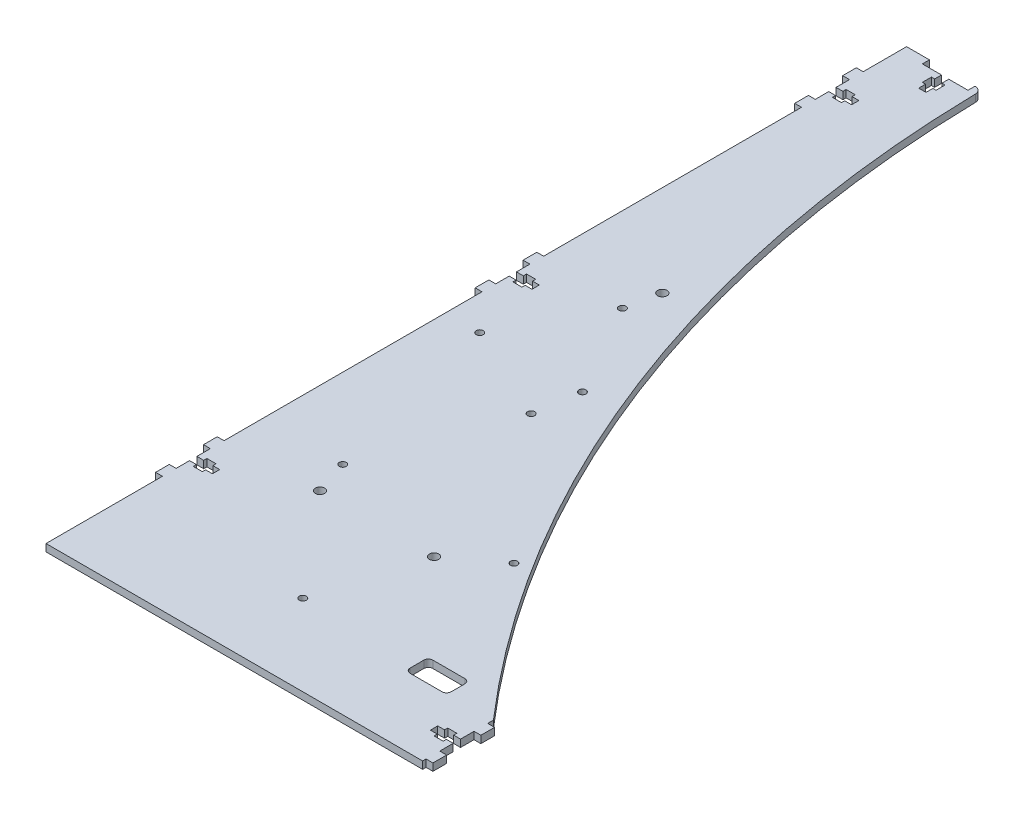
SolidWorks part; units mm, degrees
ref_plane "Alzado" through (0, 0, 0) normal (0, 0, 1) x (1, 0, 0)
ref_plane "Planta" through (0, 0, 0) normal (0, 1, 0) x (1, 0, 0)
ref_plane "Vista lateral" through (0, 0, 0) normal (1, 0, 0) x (0, 0, -1)
sketch "Croquis1" plane through (0, 0, 0) normal (0, 1, 0) x (1, 0, 0)
  line L0 (7, 66.1) -> (10, 66.1)
  line L1 (0, 0) -> (165, 0)
  line L2 (0, 0) -> (0, 51)
  line L3 (0, 377) -> (10, 377)
  line L4 (165, 0) -> (165, 1.5)
  line L5 (0, 51) -> (-3, 51)
  line L7 (0, 57) -> (-3, 57)
  line L8 (-3, 51) -> (-3, 57)
  line L9 (0, 72) -> (-3, 72)
  line L11 (0, 78) -> (-3, 78)
  line L12 (-3, 72) -> (-3, 78)
  line L13 (0, 66.1) -> (3, 66.1)
  line L15 (0, 62.9) -> (3, 62.9)
  line L16 (10, 66.1) -> (10, 62.9)
  line L17 (7, 67.5) -> (3, 67.5)
  line L18 (7, 67.5) -> (7, 66.1)
  line L19 (7, 61.5) -> (3, 61.5)
  line L20 (3, 67.5) -> (3, 66.1)
  line L21 (3, 62.9) -> (3, 61.5)
  line L22 (7, 62.9) -> (7, 61.5)
  line L23 (7, 62.9) -> (10, 62.9)
  line L24 (0, 66.1) -> (0, 72)
  line L25 (0, 78) -> (0, 191)
  line L26 (0, 57) -> (0, 62.9)
  line L27 (0, 218) -> (-3, 218)
  line L28 (-3, 212) -> (-3, 218)
  line L29 (0, 212) -> (-3, 212)
  line L30 (0, 206.1) -> (3, 206.1)
  line L31 (3, 207.5) -> (3, 206.1)
  line L32 (7, 207.5) -> (3, 207.5)
  line L33 (7, 207.5) -> (7, 206.1)
  line L34 (7, 206.1) -> (10, 206.1)
  line L35 (10, 206.1) -> (10, 202.9)
  line L36 (7, 202.9) -> (10, 202.9)
  line L37 (7, 202.9) -> (7, 201.5)
  line L38 (7, 201.5) -> (3, 201.5)
  line L39 (3, 202.9) -> (3, 201.5)
  line L40 (0, 202.9) -> (3, 202.9)
  line L41 (0, 197) -> (-3, 197)
  line L42 (-3, 191) -> (-3, 197)
  line L43 (0, 191) -> (-3, 191)
  line L44 (0, 358) -> (-3, 358)
  line L45 (-3, 352) -> (-3, 358)
  line L46 (0, 352) -> (-3, 352)
  line L47 (0, 346.1) -> (3, 346.1)
  line L48 (3, 347.5) -> (3, 346.1)
  line L49 (7, 347.5) -> (3, 347.5)
  line L50 (7, 347.5) -> (7, 346.1)
  line L51 (7, 346.1) -> (10, 346.1)
  line L52 (10, 346.1) -> (10, 342.9)
  line L53 (7, 342.9) -> (10, 342.9)
  line L54 (7, 342.9) -> (7, 341.5)
  line L55 (7, 341.5) -> (3, 341.5)
  line L56 (3, 342.9) -> (3, 341.5)
  line L57 (0, 342.9) -> (3, 342.9)
  line L58 (0, 337) -> (-3, 337)
  line L59 (-3, 331) -> (-3, 337)
  line L60 (0, 331) -> (-3, 331)
  line L61 (0, 358) -> (0, 377)
  line L62 (0, 346.1) -> (0, 352)
  line L63 (0, 337) -> (0, 342.9)
  line L64 (0, 218) -> (0, 331)
  line L65 (0, 206.1) -> (0, 212)
  line L66 (0, 197) -> (0, 202.9)
  line L67 (21.6, 373.9) -> (30, 373.9)
  line L69 (10, 377) -> (10, 373.9)
  line L70 (10, 373.9) -> (18.4, 373.9)
  line L71 (30, 377) -> (30, 373.9)
  line L73 (18.4, 373.9) -> (18.4, 370.9)
  line L74 (18.4, 363.9) -> (21.6, 363.9)
  line L75 (21.6, 373.9) -> (21.6, 370.9)
  line L76 (17, 370.9) -> (18.4, 370.9)
  line L77 (17, 370.9) -> (17, 366.9)
  line L78 (17, 366.9) -> (18.4, 366.9)
  line L79 (23, 370.9) -> (23, 366.9)
  line L80 (21.6, 370.9) -> (23, 370.9)
  line L81 (18.4, 366.9) -> (18.4, 363.9)
  line L82 (21.6, 366.9) -> (21.6, 363.9)
  line L83 (21.6, 366.9) -> (23, 366.9)
  line L84 (30, 377) -> (165, 377)
  line L85 (158, 13.4) -> (158, 12)
  line L86 (165, 1.5) -> (168, 1.5)
  line L88 (165, 7.5) -> (168, 7.5)
  line L89 (168, 1.5) -> (168, 7.5)
  line L90 (165, 22.5) -> (168, 22.5)
  line L92 (165, 28.5) -> (168, 28.5)
  line L93 (168, 22.5) -> (168, 28.5)
  line L94 (165, 16.6) -> (162, 16.6)
  line L96 (165, 13.4) -> (162, 13.4)
  line L97 (155, 16.6) -> (155, 13.4)
  line L98 (158, 18) -> (162, 18)
  line L99 (158, 18) -> (158, 16.6)
  line L100 (158, 12) -> (162, 12)
  line L101 (162, 18) -> (162, 16.6)
  line L102 (158, 16.6) -> (155, 16.6)
  line L103 (162, 13.4) -> (162, 12)
  line L104 (158, 13.4) -> (155, 13.4)
  line L105 (165, 16.6) -> (165, 22.5)
  line L106 (165, 7.5) -> (165, 13.4)
  line L107 (165, 28.5) -> (165, 377)
  dimension "D1" = 377
  dimension "D2" = 165
  dimension "D3" = 3
  dimension "D4" = 6
  dimension "D5" = 3
  dimension "D6" = 6
  dimension "D7" = 15
  dimension "D8" = 10
  dimension "D9" = 3.2
  dimension "D10" = 5.9
  dimension "D11" = 4
  dimension "D12" = 6
  dimension "D13" = 1.4
  dimension "D14" = 51
  dimension "D15" = 3
  dimension "D17" = 140
  dimension "D18" = 20
  dimension "D19" = 10
  dimension "D20" = 3.1
  dimension "D21" = 10
  dimension "D22" = 3.2
  dimension "D23" = 4
  dimension "D24" = 6
  dimension "D25" = 1.4
  dimension "D26" = 8.4
  dimension "D27" = 3
  dimension "D28" = 6
  dimension "D29" = 6
  dimension "D30" = 3
  dimension "D31" = 3
  dimension "D32" = 3.2
  dimension "D33" = 4
  dimension "D34" = 6
  dimension "D35" = 1.4
  dimension "D36" = 10
  dimension "D37" = 3
  dimension "D38" = 15
  dimension "D39" = 5.9
  dimension "D40" = 1.5
  dimension "D16" = 3
extrude "Saliente-Extruir1" add sketch "Croquis1" along normal blind 3.2
sketch "Croquis2" plane through (0, 0, 0) normal (0, -1, 0) x (1, 0, 0)
  line L0 (30, -377) -> (30, -373.9) construction
  line L1 (165, -377) -> (33, -377)
  line L2 (165, -377) -> (165, -31)
  line L3 (165, -31) -> (33, -31) construction
  line L4 (33, -377) -> (33, -31) construction
  line L5 (168, -28.5) -> (165, -28.5) construction
  arc A0 (33, -377) -> (165, -31) centre (571.7994, -384.3743) cw
  dimension "D1" = 3
  dimension "D2" = 2.5
extrude "Cortar-Extruir1" cut sketch "Croquis2" against normal up to surface (3.2 mm away) up to face at (40.46, 3.2, -192.526)
fillet "Redondeo1" radius 3 1 edges at (33, 1.6, -377)
sketch "Croquis3" plane through (0, 3.2, 0) normal (0, 1, 0) x (1, 0, 0)
  line L0 (0, 202.9) -> (0, 197) construction
  line L1 (0, 0) -> (165, 0) construction
  circle A0 centre (40, 80) radius 2.05
  circle A1 centre (90, 80) radius 2.05
  circle A2 centre (40, 230) radius 2.05
  dimension "D1" = 4.1
  dimension "D2" = 50
  dimension "D3" = 150
  dimension "D4" = 40
  dimension "D5" = 80
extrude "Cortar-Extruir2" cut sketch "Croquis3" against normal up to surface (3.2 mm away) up to face at (39.9955, 0, -192.6144)
sketch "Croquis4" plane through (0, 0, 0) normal (0, -1, 0) x (1, 0, 0)
  line L1 (0, 0) -> (165, 0) construction
  line L3 (165, -28.5) -> (165, -31) construction
  line L4 (143, -30.5) -> (129, -30.5)
  line L5 (145, -32.5) -> (145, -38.5)
  line L6 (143, -40.5) -> (129, -40.5)
  line L7 (127, -32.5) -> (127, -38.5)
  arc A14 (143, -30.5) -> (145, -32.5) centre (143, -32.5) cw
  arc A15 (127, -38.5) -> (129, -40.5) centre (129, -38.5) ccw
  arc A16 (127, -32.5) -> (129, -30.5) centre (129, -32.5) cw
  arc A17 (145, -38.5) -> (143, -40.5) centre (143, -38.5) cw
  point P38 (145, -30.5)
  point P41 (127, -40.5)
  point P46 (145, -40.5)
  dimension "D3" = 20
  dimension "D20" = 2
  dimension "D16" = 18
  dimension "D17" = 10
  dimension "D19" = 30.5
extrude "Cortar-Extruir3" cut sketch "Croquis4" against normal up to surface (3.2 mm away) up to face at (40, 3.2, -227.95)
sketch "Croquis5" plane through (0, 0, 0) normal (0, -1, 0) x (1, 0, 0)
  line L0 (0, 0) -> (165, 0) construction
  line L1 (0, -191) -> (0, -78) construction
  line L2 (127, -35.5) -> (77, -35.5) construction
  line L3 (127, -32.5) -> (127, -38.5) construction
  circle A0 centre (110, -95) radius 1.55
  circle A1 centre (35, -95) radius 1.55
  circle A2 centre (15, -175) radius 1.55
  circle A3 centre (60, -175) radius 1.55
  circle A4 centre (77, -35.5) radius 1.55
  circle A5 centre (37, -215.5) radius 1.55
  circle A6 centre (57, -155.5) radius 1.55
  dimension "D1" = 3.1
  dimension "D2" = 75
  dimension "D3" = 95
  dimension "D4" = 35
  dimension "D5" = 45
  dimension "D6" = 15
  dimension "D7" = 80
  dimension "D8" = 50
  dimension "D9" = 180
  dimension "D10" = 40
  dimension "D11" = 120
  dimension "D12" = 20
extrude "Cortar-Extruir4" cut sketch "Croquis5" against normal up to surface (3.2 mm away) up to face at (136, 3.2, -35.5)
